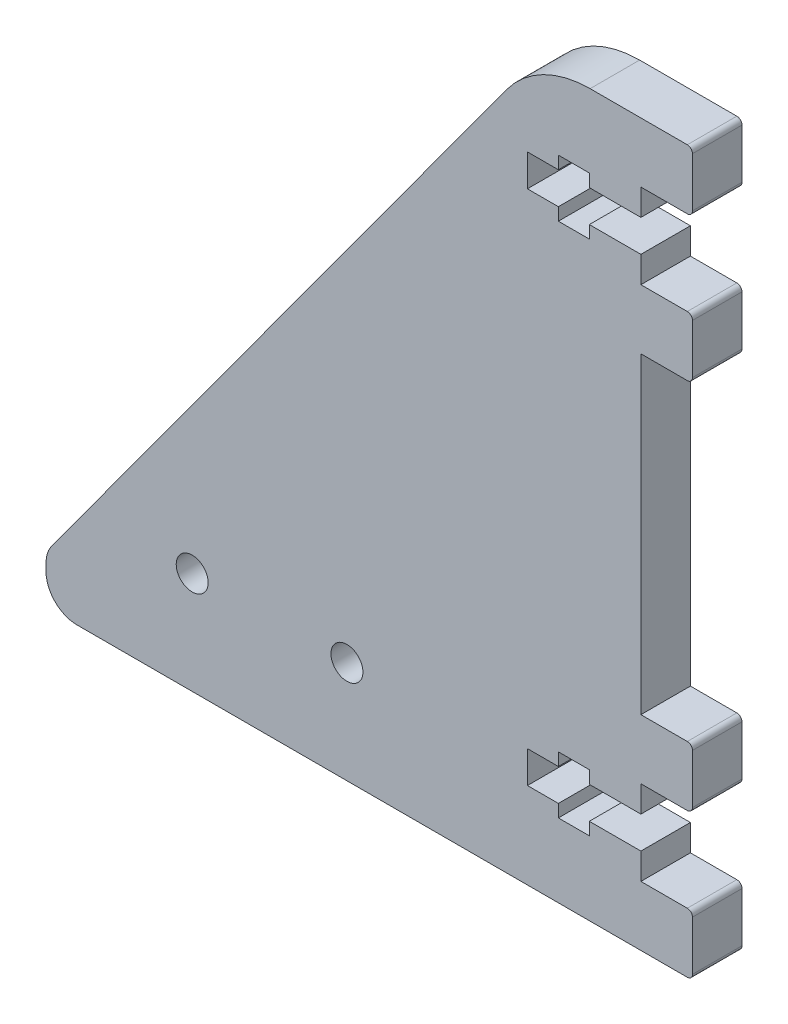
SolidWorks part; units mm, degrees
ref_plane "Plan de face" through (0, 0, 0) normal (0, 0, 1) x (1, 0, 0)
ref_plane "Plan de dessus" through (0, 0, 0) normal (0, 1, 0) x (1, 0, 0)
ref_plane "Plan de droite" through (0, 0, 0) normal (1, 0, 0) x (0, 0, -1)
ref_plane "Plan1" through (0, 0, 0) normal (0, 0, -1) x (-1, 0, 0)
sketch "Esquisse1" plane through (0, 0, 0) normal (0, 0, -1) x (-1, 0, 0)
  line L0 (38, -9.9) -> (38, 60)
  line L1 (38, 60) -> (-12, 60)
  line L2 (-12, 60) -> (-12, 11.9)
  line L3 (-12, 9.9) -> (-17, 9.9)
  line L4 (-17, 9.9) -> (-17, 4.1)
  line L5 (-17, 4.1) -> (-12, 4.1)
  line L6 (-12, 2.1) -> (-12, -2.1)
  line L7 (-12, -4.1) -> (-17, -4.1)
  line L8 (-17, -4.1) -> (-17, -9.9)
  line L9 (-17, -9.9) -> (38, -9.9)
  arc A0 (-12, 11.9) -> (-12, 9.9) centre (-12, 10.9) cw
  arc A1 (-12, 4.1) -> (-12, 2.1) centre (-12, 3.1) cw
  arc A2 (-12, -2.1) -> (-12, -4.1) centre (-12, -3.1) cw
extrude "Boss.-Extru.1" add sketch "Esquisse1" against normal blind 4.8
sketch "Esquisse2" plane through (0, 0, 4.8) normal (0, 0, 1) x (1, 0, 0)
  line L0 (-38, -5.25) -> (7, -5.25)
  line L1 (7, -3.25) -> (7, 3.25)
  line L2 (7, 5.25) -> (-38, 5.25)
  line L3 (-38, 5.25) -> (-38, -5.25)
  arc A0 (7, -5.25) -> (7, -3.25) centre (7, -4.25) ccw
  arc A1 (7, 3.25) -> (7, 5.25) centre (7, 4.25) ccw
extrude "Enlèv. mat.-Extru.1" cut sketch "Esquisse2" against normal blind 2.3
draft "Dépouille1" type of draft neutral plane draft angle 36.152 faces to draft 1 face at (-38, 12.525, 3.025) neutral plane through (7, 5.25, 2.5) neutral plane normal (0, -1, 0) reverse direction yes parameters "D1"=36.152
hole_wizard "Diamètre du perçage Ø3.1 (3.1)1" positions "Esquisse4" profile "Esquisse3" hole size "Ø3.1" standard "Ansi Metric"
sketch "Esquisse4" plane through (0, 0, 0) normal (0, 0, -1) x (-1, 0, 0)
  point P1 (16.5, 0)
  point P2 (31.5, 0)
sketch "Esquisse3" plane through (-16.5, 0, 0) normal (1, 0, 0) x (0, 1, 0)
  line L0 (0, 0) -> (0, 4.8)
  line L1 (0, 4.8) -> (1.55, 4.8)
  line L2 (1.55, 4.8) -> (1.55, 0)
  line L5 (1.55, 0) -> (0, 0)
  line L11 (0, -6.35) -> (0, 107.95) construction
  dimension "Diamètre du perçage jusqu'au prochain" = 3.1
  dimension "Profondeur du perçage jusqu'au prochain" = 4.8
fillet "Congé1" radius 10 1 edges at (2, 60, 2.4) tangent propagation no
sketch "Esquisse5" plane through (0, 0, 4.8) normal (0, 0, 1) x (1, 0, 0)
  line L0 (7, 5.25) -> (-38, 5.25) construction
  line L1 (-45.6712, -5.25) -> (9.1334, -5.25)
  line L2 (-45.6712, -5.25) -> (-45.6712, 5.25)
  line L3 (-45.6712, 5.25) -> (9.1334, 5.25)
  line L4 (9.1334, -5.25) -> (9.1334, 5.25)
  line L5 (12, -4.1) -> (17, -4.1) construction
  line L6 (-45.6712, -5.25) -> (-49.0685, -5.25)
  line L7 (-45.6712, -5.25) -> (-45.6712, -9.9)
  line L8 (-45.6712, -9.9) -> (-49.0685, -9.9)
  line L9 (-49.0685, -5.25) -> (-49.0685, -9.9)
  line L10 (12, -4.1) -> (10.1478, -4.1)
  line L11 (12, -4.1) -> (12, 15.7428)
  line L12 (12, 15.7428) -> (10.1478, 15.7428)
  line L13 (10.1478, -4.1) -> (10.1478, 15.7428)
  line L14 (-49.0685, -9.9) -> (-38, 5.25)
  circle A0 centre (-31.5, 0) radius 1.55
  circle A1 centre (-16.5, 0) radius 1.55
  arc A3 (12, -2.1) -> (12, -4.1) centre (12, -3.1) ccw construction
  line M5 (-38, 5.25) -> (7, 5.25)
  arc M6 (7, 5.25) -> (7, 3.25) centre (7, 4.25) cw
  line M7 (7, 3.25) -> (7, -3.25)
  arc M8 (7, -3.25) -> (7, -5.25) centre (7, -4.25) cw
  line M9 (7, -5.25) -> (-45.6712, -5.25)
  line M10 (-45.6712, -5.25) -> (-49.0685, -9.9)
  line M11 (-49.0685, -9.9) -> (17, -9.9)
  arc M14 (12, -4.1) -> (12, -2.1) centre (12, -3.1) cw
  line M15 (12, -2.1) -> (12, 2.1)
  arc M16 (12, 2.1) -> (12, 4.1) centre (12, 3.1) cw
  arc M20 (12, 9.9) -> (12, 11.9) centre (12, 10.9) cw
  line M21 (12, 11.9) -> (12, 60)
  dimension "D1" = 0
extrude "Boss.-Extru.2" add sketch "Esquisse5" against normal up to surface (4.8 mm away) contours L14 A1 A0 M9 M8 M7 M6 M5 | L13 L10 L11 L12 M14 M15 M16 M20 M21 | L11 M14 | L11 M16 | L11 M20 region at (-41.394, -0.3226, 4.8) region at (11.5756, -3.1, 4.8) region at (11.0001, 6.1432, 4.8) region at (11.5756, 3.1, 4.8) region at (11.5756, 10.9, 4.8) up to face at (-18.05, 0, 0)
extrude "Enlèv. mat.-Extru.2" cut sketch "Esquisse5<4>" against normal through all contours L7 M10 M11 region at (-46.8037, -8.35, 4.8)
sketch "Esquisse5<4>" plane through (0, 0, 4.8) normal (0, 0, 1) x (1, 0, 0) same geometry as "Esquisse5"
sketch "Esquisse6" plane through (0, 0, 4.8) normal (0, 0, 1) x (1, 0, 0)
  line L0 (12, -1.55) -> (1, -1.55)
  line L1 (12, -1.55) -> (12, 1.55)
  line L2 (12, 1.55) -> (1, 1.55)
  line L3 (1, -1.55) -> (1, 1.55)
  line L4 (4, -2.77) -> (7, -2.77)
  line L5 (4, -2.77) -> (4, 2.78)
  line L6 (4, 2.78) -> (7, 2.78)
  line L7 (7, -2.77) -> (7, 2.78)
  line L9 (17, 4.1) -> (12, 4.1) construction
  line L10 (12, 4.1) -> (12, -4.1) construction
  line L12 (12, 48.55) -> (1, 48.55)
  line L13 (12, 48.55) -> (12, 51.65)
  line L14 (12, 51.65) -> (1, 51.65)
  line L15 (1, 48.55) -> (1, 51.65)
  line L16 (4, 47.33) -> (7, 47.33)
  line L17 (4, 47.33) -> (4, 52.88)
  line L18 (4, 52.88) -> (7, 52.88)
  line L19 (7, 47.33) -> (7, 52.88)
  line L20 (7.0786, 60) -> (12, 60) construction
  line L21 (12, 60) -> (12, 9.9) construction
  line M11 (12, -4.1) -> (12, 4.1)
  line M15 (12, 9.9) -> (12, 60)
  dimension "D1" = 3
  dimension "D2" = 5
  dimension "D3" = 3.1
  dimension "D4" = 5.55
  dimension "D5" = 1.23
  dimension "D6" = 2.55
  dimension "D7" = 0
  dimension "D8" = 3
  dimension "D9" = 5
  dimension "D10" = 3.1
  dimension "D11" = 5.55
  dimension "D12" = 1.23
  dimension "D13" = 8.35
  dimension "D14" = 0
  dimension "D15" = 3
  dimension "D16" = 3
extrude "Enlèv. mat.-Extru.3" cut sketch "Esquisse6" against normal through all contours L0 L5 L2 L3 | L0 L7 L2 L5 | L4 L7 L0 L5 | L7 L0 L2 M11 | L2 L7 L6 L5 | L16 L19 L12 L17 | L12 L19 L14 L17 | L12 L17 L14 L15 | L14 L19 L18 L17 | L19 L12 L14 M15 region at (9.5, 0, 4.8) region at (5.5, -2.16, 4.8) region at (5.5, 0, 4.8) region at (2.5, 0, 4.8) region at (5.5, 2.165, 4.8) region at (9.5, 50.1, 4.8) region at (5.5, 47.94, 4.8) region at (5.5, 50.1, 4.8) region at (2.5, 50.1, 4.8) region at (5.5, 52.265, 4.8)
sketch "Esquisse7" plane through (0, 0, 4.8) normal (0, 0, 1) x (1, 0, 0)
  line L1 (12, 48.55) -> (12, 9.9) construction
  line L2 (12, 60) -> (17, 60)
  line L3 (12, 60) -> (12, 54.2)
  line L4 (12, 54.2) -> (17, 54.2)
  line L5 (17, 60) -> (17, 54.2)
  line L6 (12, 46) -> (17, 46)
  line L7 (12, 46) -> (12, 40.2)
  line L8 (12, 40.2) -> (17, 40.2)
  line L9 (17, 46) -> (17, 40.2)
  line L12 (12, 48.55) -> (7, 48.55) construction
  dimension "D1" = 5.8
  dimension "D2" = 5.8
  dimension "D3" = 2.55
  dimension "D4" = 5
  dimension "D5" = 5
extrude "Boss.-Extru.3" add sketch "Esquisse7" against normal up to surface (4.8 mm away) up to face at (-18.05, 0, 0)
fillet "Congé2" radius 3 2 edges at (-45.6712, -5.25, 2.4) (-45.6712, -9.9, 2.4)
fillet "Congé3" radius 0.5 8 edges at (17, 40.2, 2.4) (17, 46, 2.4) (17, 60, 2.4) (17, 54.2, 2.4) (17, 9.9, 2.4) (17, 4.1, 2.4) (17, -4.1, 2.4) (17, -9.9, 2.4)
